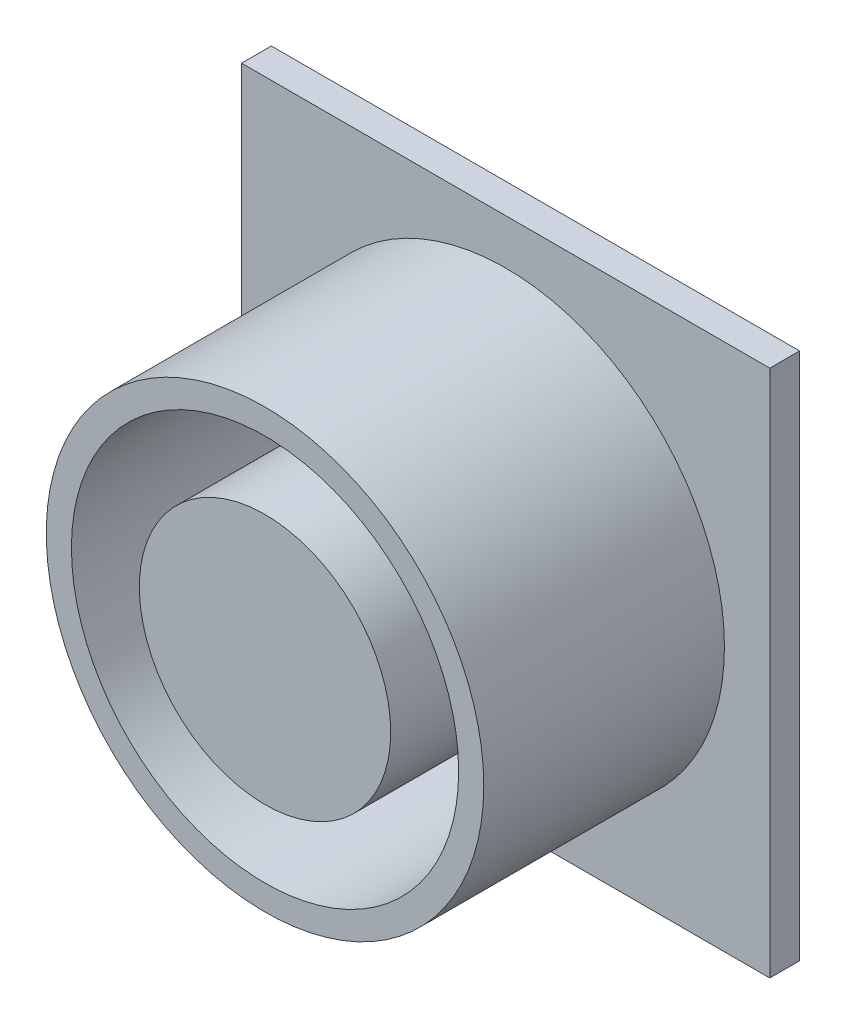
SolidWorks part; units mm, degrees
ref_plane "Front Plane" through (0, 0, 0) normal (0, 0, 1) x (1, 0, 0)
ref_plane "Top Plane" through (0, 0, 0) normal (0, 1, 0) x (1, 0, 0)
ref_plane "Right Plane" through (0, 0, 0) normal (1, 0, 0) x (0, 0, -1)
sketch "Sketch1" plane through (0, 0, 0) normal (0, 0, 1) x (1, 0, 0)
  line L1 (-35.146, -35.146) -> (35.146, -35.146)
  line L2 (-35.146, -35.146) -> (-35.146, 35.146)
  line L3 (-35.146, 35.146) -> (35.146, 35.146)
  line L4 (35.146, -35.146) -> (35.146, 35.146)
  line L5 (-35.146, -35.146) -> (35.146, 35.146) construction
  line L6 (-35.146, 35.146) -> (35.146, -35.146) construction
  circle A0 centre (0, 0) radius 25.7683
  circle A1 centre (0, 0) radius 16.7259
  circle A2 centre (0, 0) radius 29.1113
  point P0 (0, 0)
  dimension "D2" = 51.5366
  dimension "D3" = 33.4518
  dimension "D4" = 58.2227
  dimension "D1" = 70.292
extrude "Boss-Extrude1" add sketch "Sketch1" along normal blind 3.9624 contours L2 L3 L4 L1
extrude "Boss-Extrude2" add sketch "Sketch1<3>" along normal blind 32.0294 from surface contours A2 A0 region at (-28.2879, 0, 0) starting at face at (0, 0, 3.9624)
sketch "Sketch1<3>" plane through (0, 0, 0) normal (0, 0, 1) x (1, 0, 0) same geometry as "Sketch1"
extrude "Boss-Extrude3" add sketch "Sketch1<4>" along normal blind 32.0294 from surface contours A1 region at (0, 0, 0) starting at face at (29.1113, 0, 3.9624)
sketch "Sketch1<4>" plane through (0, 0, 0) normal (0, 0, 1) x (1, 0, 0) same geometry as "Sketch1"
